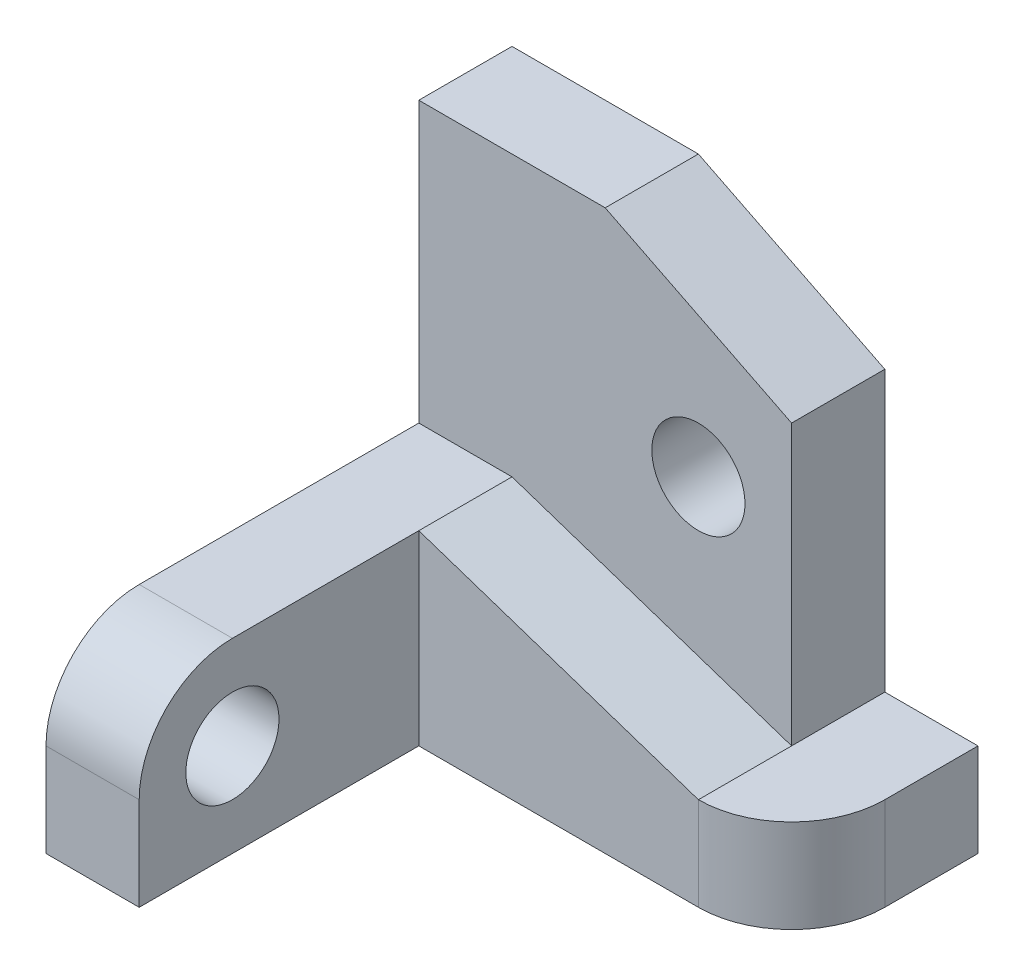
SolidWorks part; units mm, degrees
ref_plane "前基準面" through (0, 0, 0) normal (0, 0, 1) x (1, 0, 0)
ref_plane "上基準面" through (0, 0, 0) normal (0, 1, 0) x (1, 0, 0)
ref_plane "右基準面" through (0, 0, 0) normal (1, 0, 0) x (0, 0, -1)
sketch "草圖1" plane through (0, 0, 0) normal (0, 1, 0) x (1, 0, 0)
  line L0 (20, 5) -> (20, 0)
  line L1 (0, 0) -> (20, 0)
  line L2 (0, 0) -> (0, 10)
  line L3 (0, 10) -> (25, 10)
  line L4 (25, 5) -> (25, 10)
  line L5 (20, 10) -> (0, 10)
  line L6 (20, 10) -> (20, 5)
  line L7 (20, 5) -> (0, 5)
  line L8 (0, 10) -> (0, 5)
  arc A0 (20, 0) -> (25, 5) centre (20, 5) ccw
  dimension "D5" = 5
  dimension "D1" = 10
  dimension "D2" = 25
  dimension "D3" = 5
  dimension "D4" = 5
extrude "填料-伸長1" add sketch "草圖1" along normal blind 5 contours L0 A0 L4 L3 L6 region at (22.3337, 0, -5.4667)
extrude "填料-伸長2" add sketch "草圖1<3>" along normal blind 10 contours L0 L7 L2 L1 region at (10, 0, -2.5)
sketch "草圖1<3>" plane through (0, 0, 0) normal (0, 1, 0) x (1, 0, 0) same geometry as "草圖1"
extrude "填料-伸長3" add sketch "草圖1<4>" along normal blind 25 contours L7 L6 L3 L2 region at (10, 0, -7.5)
sketch "草圖1<4>" plane through (0, 0, 0) normal (0, 1, 0) x (1, 0, 0) same geometry as "草圖1"
sketch "草圖2" plane through (0, 0, -5) normal (0, 0, 1) x (1, 0, 0)
  line L0 (20, 25) -> (0, 25) construction
  line L1 (10, 25) -> (20, 20)
  line L3 (20, 20) -> (20, 25)
  line L4 (20, 25) -> (10, 25)
  line L5 (20, 25) -> (20, 10) construction
  circle A0 centre (15, 15) radius 2.5
  point P12 (0, 0)
  dimension "D5" = 5
  dimension "D1" = 10
  dimension "D2" = 5
  dimension "D3" = 5
  dimension "D4" = 10
extrude "除料-伸長1" cut sketch "草圖2" against normal blind 25
sketch "草圖3" plane through (0, 0, 0) normal (0, 0, 1) x (1, 0, 0)
  line L0 (20, 5) -> (5, 10)
  line L1 (0, 10) -> (20, 10) construction
  line L2 (5, 10) -> (20, 10)
  line L3 (20, 10) -> (20, 5)
  dimension "D1" = 15
extrude "除料-伸長2" cut sketch "草圖3" against normal up to surface (5 mm away) up to face at (10, 18, -5)
sketch "草圖4" plane through (0, 0, 0) normal (1, 0, 0) x (0, 0, -1)
  line L0 (0, 10) -> (-10, 10)
  line L1 (-15, 5) -> (-15, 0)
  line L2 (-15, 0) -> (0, 0)
  line L3 (0, 10) -> (0, 5) construction
  line L4 (0, 10) -> (0, 0)
  arc A0 (-10, 10) -> (-15, 5) centre (-10, 5) ccw
  circle A1 centre (-10, 5) radius 2.5
  dimension "D2" = 5
  dimension "D3" = 5
  dimension "D1" = 15
extrude "填料-伸長4" add sketch "草圖4" along normal blind 5
